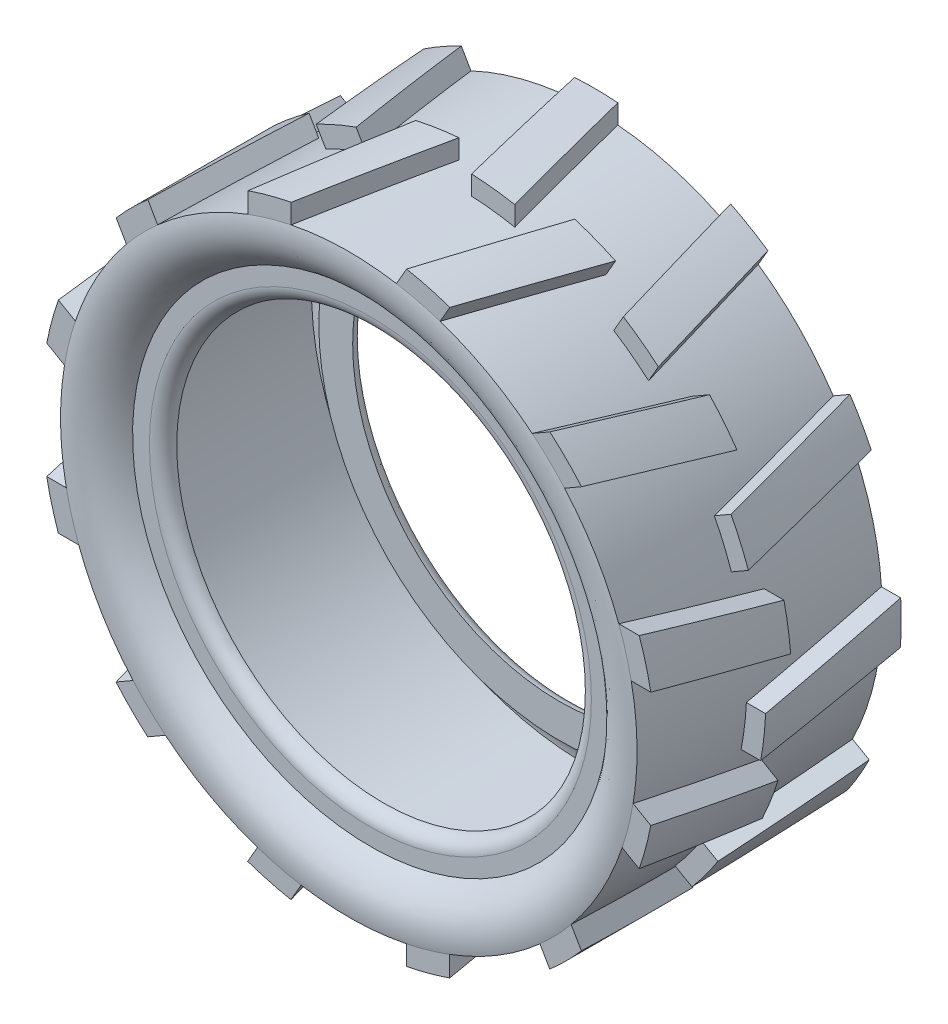
SolidWorks part; units mm, degrees
material "ABS"
ref_plane "Спереди" through (0, 0, 0) normal (0, 0, 1) x (1, 0, 0)
ref_plane "Сверху" through (0, 0, 0) normal (0, 1, 0) x (1, 0, 0)
ref_plane "Справа" through (0, 0, 0) normal (1, 0, 0) x (0, 0, -1)
sketch "Эскиз1" plane through (0, 0, 0) normal (1, 0, 0) x (0, 0, -1)
  line L0 (-131.0476, 0) -> (127.548, 0) construction
  line L1 (0, 0) -> (0, 104.7617) construction
  line L2 (0, 60) -> (25.5, 60)
  line L3 (21, 49.5) -> (21, 46)
  line L5 (18.3095, 50.0522) -> (18.3095, 46)
  line L14 (18.3095, 46) -> (18.3095, 43)
  line L16 (25.5, 60) -> (21, 49.5) construction
  line L17 (0, 57.3095) -> (21.4198, 57.3095) construction
  line L18 (21.4198, 57.3095) -> (18.3095, 50.0522) construction
  line L20 (19.831, 51.1228) -> (18.3095, 50.0522)
  line L21 (-19.831, 51.1228) -> (-18.3095, 50.0522)
  line L23 (-18.3095, 46) -> (-18.3095, 43)
  line L24 (-18.3095, 50.0522) -> (-18.3095, 46)
  line L25 (-21, 49.5) -> (-21, 46)
  line L26 (0, 60) -> (-25.5, 60)
  line L27 (0, 57) -> (23.7272, 57)
  line L28 (0, 57) -> (-23.7272, 57)
  line L32 (0, 58) -> (23.7544, 58) construction
  arc A0 (21, 46) -> (18.3095, 43) centre (18, 45.984) cw
  arc A1 (-21, 46) -> (-18.3095, 43) centre (-18, 45.984) ccw
  spline S0 degree 2 poles (25.5, 60) (26.8739, 53.7315) (21, 49.5) knots 0 0 0 1 1 1
  spline S1 degree 1 poles (23.7544, 58) (19.831, 51.1228) knots 0 0 1 1 construction
  spline S2 degree 3 poles (23.7544, 58) (23.7671, 57.6775) (23.7509, 57.0178) (23.5531, 55.812) (23.1145, 54.6722) (22.4028, 53.5614) (21.7154, 52.7344) (20.8801, 51.9263) (20.1802, 51.3744) (19.831, 51.1228) knots 0.157276 0.157276 0.157276 0.157276 0.262617 0.367957 0.578638 0.683979 0.789319 0.89466 1 1 1 1 only from (23.7272, 57) to (19.831, 51.1228)
  spline S3 degree 3 poles (-23.7272, 57) (-23.6981, 56.6959) (-23.5494, 55.8023) (-23.1145, 54.6722) (-22.4028, 53.5614) (-21.7154, 52.7344) (-20.8801, 51.9263) (-20.1802, 51.3744) (-19.831, 51.1228) knots 0.26618 0.26618 0.26618 0.26618 0.367957 0.578638 0.683979 0.789319 0.89466 1 1 1 1
  spline S4 degree 2 poles (-25.5, 60) (-26.8739, 53.7315) (-21, 49.5) knots 0 0 0 1 1 1
  point P32 (-23.7544, 57)
  dimension "D8" = 3
  dimension "D9" = 3
  dimension "D10" = 21
  dimension "D1" = 46
  dimension "D2" = 60
  dimension "D3" = 3.5
  dimension "D5" = 25.5
  dimension "D6" = 1.8603
  dimension "D7" = 4.0522
  dimension "D11" = 3
  dimension "D4" = 2
revolve "Повернуть1" add sketch "Эскиз1" angle 360 about L0
ref_plane "Плоскость1" through (0, 65, 0) normal (0, 1, 0) x (1, 0, 0)
sketch "Эскиз2" plane through (0, 65, 0) normal (0, 1, 0) x (1, 0, 0)
  line L0 (0, 31.0851) -> (0, -28.8708) construction
  line L1 (-48.8845, 0) -> (54.335, 0) construction
  line L2 (-5.2599, 2.6858) -> (-12, -25.5)
  line L3 (60, -25.5) -> (-60, -25.5) construction
  line L4 (-12, -25.5) -> (-21, -25.5)
  line L5 (-21, -25.5) -> (-14.2599, 2.6858)
  line L6 (-14.2599, 2.6858) -> (-5.2599, 2.6858)
  line L11 (5, 25.5) -> (-4, 25.5)
  line L12 (11.7401, -2.6858) -> (5, 25.5)
  line L13 (-4, 25.5) -> (2.7401, -2.6858)
  line L14 (2.7401, -2.6858) -> (11.7401, -2.6858)
  dimension "D1" = 9
  dimension "D2" = 21
  dimension "D3" = 5
extrude "Бобышка-Вытянуть1" add sketch "Эскиз2" against normal up to surface (6.7192 mm away) up to face at (60, 0, -25.5)
pattern_circular "Круговой массив1" count 12 over 360 about axis through (0, 0, 131.0476) along (0, 0, 1) of "Бобышка-Вытянуть1" reverse direction yes
sketch "Эскиз3" plane through (0, 0, 21) normal (0, 0, 1) x (1, 0, 0)
  circle A1 centre (0, 0) radius 64
  circle A2 centre (0, 0) radius 81.6428
  dimension "D1" = 128
extrude "Вырез-Вытянуть1" cut sketch "Эскиз3" against normal through all both and the other way through all
